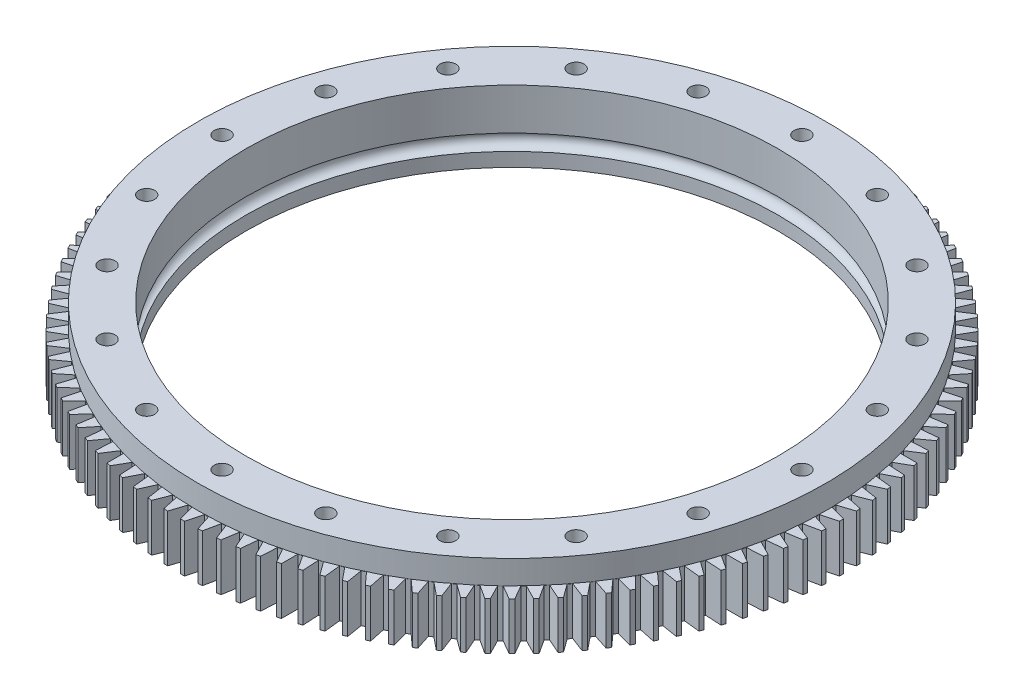
SolidWorks part; units mm, degrees
ref_plane "Plan de face" through (0, 0, 0) normal (0, 0, 1) x (1, 0, 0)
ref_plane "Plan de dessus" through (0, 0, 0) normal (0, 1, 0) x (1, 0, 0)
ref_plane "Plan de droite" through (0, 0, 0) normal (1, 0, 0) x (0, 0, -1)
sketch "Esquisse1" plane through (0, 0, 0) normal (0, 0, 1) x (1, 0, 0)
  line L0 (0, 37.5) -> (0, 90)
  line L1 (0, 0) -> (80, 0)
  line L2 (0, 0) -> (0, 17.5)
  line L3 (0, 90) -> (80, 90)
  line L4 (80, 0) -> (80, 90)
  line L5 (0, 0) -> (-336, 0) construction
  line L6 (-336, 0) -> (-336, 134.4959) construction
  arc A0 (0, 17.5) -> (0, 37.5) centre (0, 27.5) ccw
  dimension "D3" = 10
  dimension "D1" = 80
  dimension "D2" = 90
  dimension "D4" = 62.5
  dimension "D5" = 336
revolve "Révolution1" add sketch "Esquisse1" angle 360 about L6
sketch "Esquisse2" plane through (0, 90, 0) normal (0, 1, 0) x (1, 0, 0)
  circle A0 centre (30, 0) radius 10
  circle A1 centre (-336, 0) radius 336 construction
  dimension "D1" = 366
extrude "Enlèv. mat.-Extru.1" cut sketch "Esquisse2" against normal blind 30
pattern_circular "Répétition circulaire1" count 20 over 360 of "Enlèv. mat.-Extru.1"
sketch "Esquisse3" plane through (0, 0, 0) normal (0, -1, 0) x (1, 0, 0)
  line L0 (-336, 0) -> (80, 0) construction
  line L1 (-336, 0) -> (79.4299, -21.7718) construction
  line L5 (-336, 0) -> (79.8574, -10.8896) construction
  line L6 (59.9462, -12.8699) -> (60.0772, -7.8699)
  line L9 (79.6377, -19.2804) -> (80.0772, -2.4988)
  line L10 (60.0772, -7.8699) -> (80.0772, -2.4988)
  line L11 (59.9462, -12.8699) -> (79.6377, -19.2804)
  circle A0 centre (-336, 0) radius 416 construction
  point P6 (0, 0)
  point P11 (60.0117, -10.3699)
  point P12 (60.0117, -10.3699)
  point P15 (79.8574, -10.8896)
  point P16 (0, 0)
  point P17 (0, 0)
  dimension "D1" = 5
  dimension "D2" = 1.5
  dimension "D3" = 20
  dimension "D4" = 3
  dimension "D5" = 2.5
extrude "Enlèv. mat.-Extru.2" cut sketch "Esquisse3" against normal blind 60
pattern_circular "Répétition circulaire2" count 120 over 360 of "Enlèv. mat.-Extru.2"
sketch "Esquisse5" plane through (0, 90, 0) normal (0, 1, 0) x (1, 0, 0)
  circle A1 centre (-336, 0) radius 416 construction
  circle A2 centre (-336, 0) radius 396
  circle A4 centre (-336, 0) radius 416
  circle A7 centre (-336, 0) radius 396
  circle M24 centre (-336, 0) radius 416
  dimension "D1" = 20
extrude "Enlèv. mat.-Extru.3" cut sketch "Esquisse5" against normal blind 30 contours A7 M24 region at (-740.2337, 90, 0)
